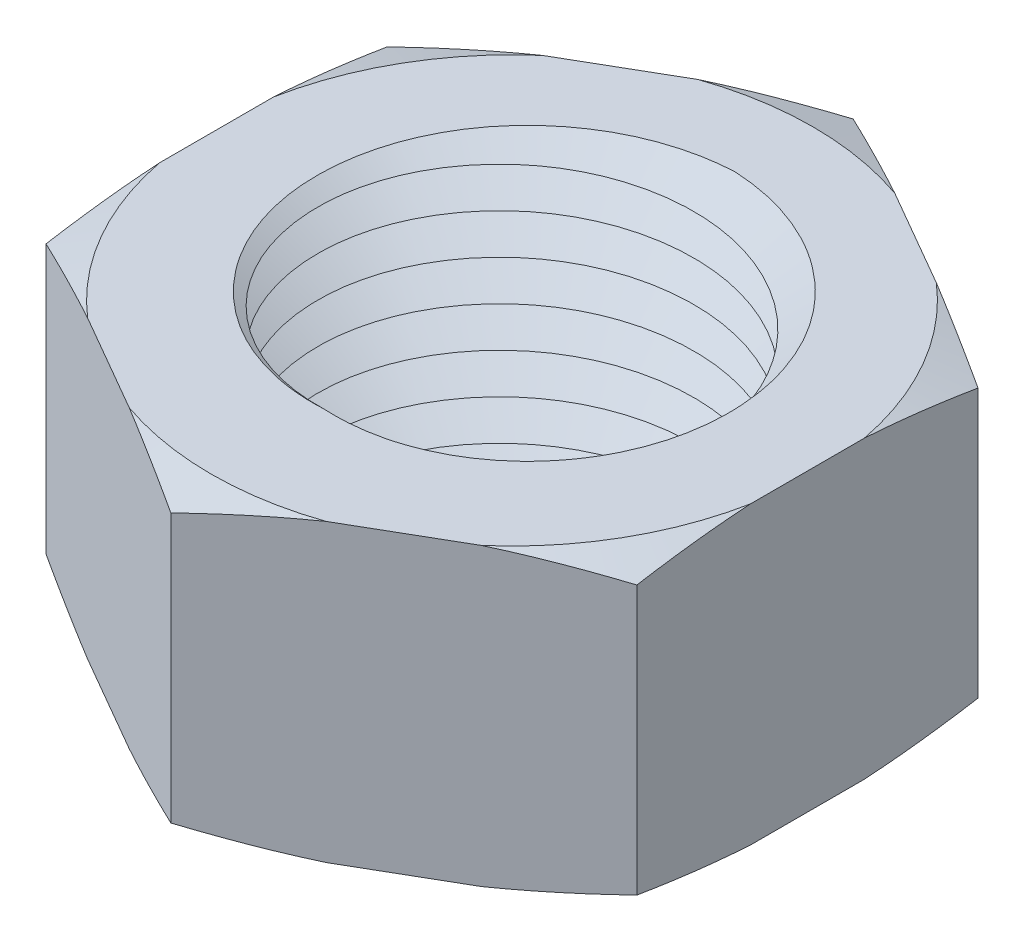
SolidWorks part; units mm, degrees
ref_plane "前视基准面" through (0, 0, 0) normal (0, 0, 1) x (1, 0, 0)
ref_plane "上视基准面" through (0, 0, 0) normal (0, 1, 0) x (1, 0, 0)
ref_plane "右视基准面" through (0, 0, 0) normal (1, 0, 0) x (0, 0, -1)
sketch "草图1" plane through (0, 0, 0) normal (0, 1, 0) x (1, 0, 0)
  line L1 (0, 12.7017) -> (-11, 6.3509)
  line L2 (-11, 6.3509) -> (-11, -6.3509)
  line L3 (-11, -6.3509) -> (0, -12.7017)
  line L4 (0, -12.7017) -> (11, -6.3509)
  line L5 (11, -6.3509) -> (11, 6.3509)
  line L6 (11, 6.3509) -> (0, 12.7017)
  circle A0 centre (0, 0) radius 11 construction
  circle A1 centre (0, 0) radius 7
  dimension "D2" = 14
  dimension "D1" = 22
extrude "凸台-拉伸1" add sketch "草图1" along normal mid plane 11
ref_plane "基准面1" through (0, 0, 0) normal (-0.5, 0, 0.866) x (0.866, 0, 0.5)
sketch "草图2" plane through (0, 0, 0) normal (-0.5, 0, 0.866) x (0.866, 0, 0.5)
  line L0 (11.2017, 5.5) -> (12.7017, 5.5)
  line L1 (6.3509, 5.5) -> (12.7017, 5.5) construction
  line L2 (12.7017, 5.5) -> (12.7017, 5)
  line L3 (12.7017, 5.5) -> (12.7017, -5.5) construction
  line L4 (12.7017, 5) -> (11.2017, 5.5)
  line L5 (0, 0) -> (0, 17.8732) construction
  line L6 (0, 0) -> (20.8438, 0) construction
  line L7 (12.7017, -5) -> (11.2017, -5.5)
  line L8 (12.7017, -5.5) -> (12.7017, -5)
  line L9 (11.2017, -5.5) -> (12.7017, -5.5)
  dimension "D1" = 0.5
  dimension "D2" = 1.5
revolve "切除-旋转1" cut sketch "草图2" angle 360 about L5
sketch "草图3" plane through (0, 5.5, 0) normal (0, 1, 0) x (1, 0, 0)
  circle A0 centre (0, 0) radius 7 construction
  circle A1 centre (0, 0) radius 7
curve "螺旋线/涡状线1" pitch 1.5 height 11 radius 7 centre (0, 5.5, 0) axis (0, -1, 0) start towards (0, 0, -1)
sketch "草图5" plane through (0, 0, 0) normal (1, 0, 0) x (0, 0, -1)
  line L0 (7, 6.2505) -> (7, 4.7495)
  line L1 (7, 4.7495) -> (8.2999, 5.5)
  line L2 (8.2999, 5.5) -> (7, 6.2505)
  point P2 (0, 0)
  point P4 (8.3, 5.6385)
  point P5 (7, 5.5)
  point P7 (0, 0)
  point P8 (8.3, 5.6055)
  dimension "D1" = 60
  dimension "D3" = 1.501
sweep "切除-扫描5" cut profiles "草图5" path "螺旋线/涡状线1" align with end faces yes
